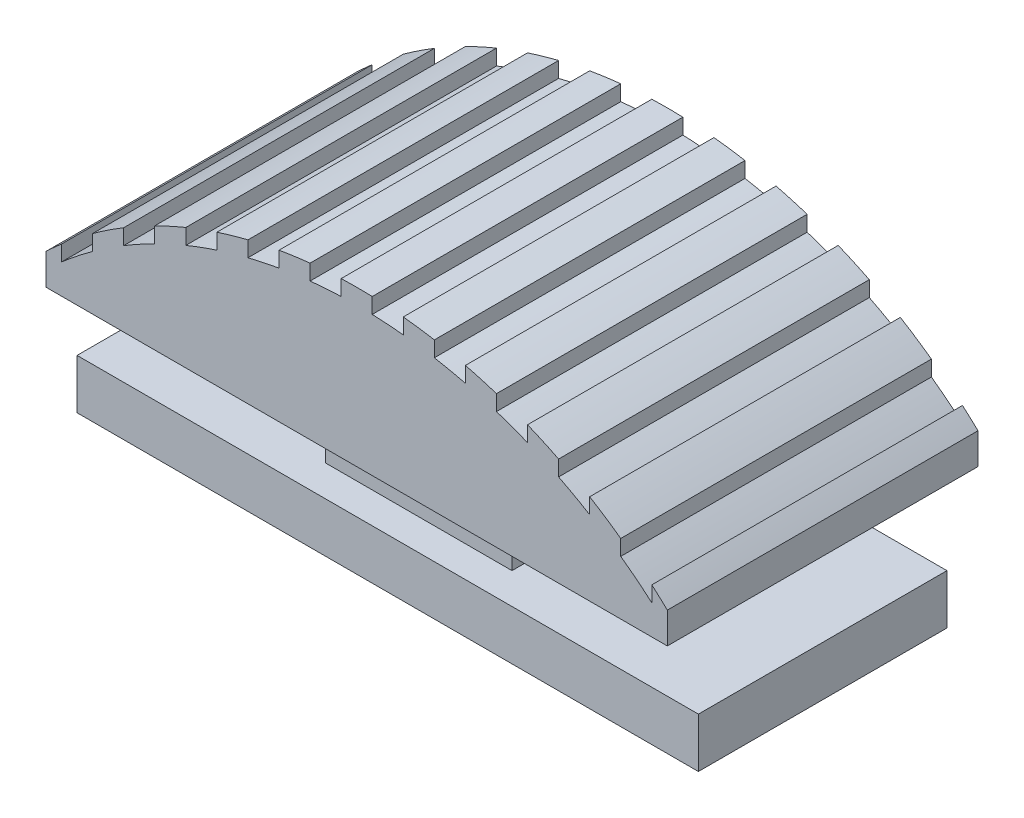
SolidWorks part; units mm, degrees
ref_plane "前视基准面" through (0, 0, 0) normal (0, 0, 1) x (1, 0, 0)
ref_plane "上视基准面" through (0, 0, 0) normal (0, 1, 0) x (1, 0, 0)
ref_plane "右视基准面" through (0, 0, 0) normal (1, 0, 0) x (0, 0, -1)
sketch "草图1" plane through (0, 0, 0) normal (0, 1, 0) x (1, 0, 0)
  line L0 (-4.9469, 0) -> (7.0243, 0) construction
  line L1 (-5, 2.5) -> (5, 2.5)
  line L2 (-5, 2.5) -> (-5, -2.5)
  line L3 (-5, -2.5) -> (5, -2.5)
  line L4 (5, 2.5) -> (5, -2.5)
  line L5 (0, 3.9764) -> (0, -4.0821) construction
  dimension "D1" = 5
  dimension "D2" = 10
extrude "凸台-拉伸1" add sketch "草图1" along normal blind 0.5
sketch "草图2" plane through (0, 0.5, 0) normal (0, 1, 0) x (1, 0, 0)
  line L0 (-5.4747, 0) -> (5.3846, 0) construction
  line L1 (-1.5, 1.5) -> (1.5, 1.5)
  line L2 (-1.5, 1.5) -> (-1.5, -1.5)
  line L3 (-1.5, -1.5) -> (1.5, -1.5)
  line L4 (1.5, 1.5) -> (1.5, -1.5)
  line L5 (0, 3.3379) -> (0, -3.1277) construction
  dimension "D1" = 3
  dimension "D2" = 3
extrude "凸台-拉伸2" add sketch "草图2" along normal blind 0.5
sketch "草图3" plane through (0, 1, 0) normal (0, 1, 0) x (1, 0, 0)
  line L1 (-5, 2.5) -> (5, 2.5)
  line L2 (-5, 2.5) -> (-5, -2.5)
  line L3 (-5, -2.5) -> (5, -2.5)
  line L4 (5, 2.5) -> (5, -2.5)
extrude "凸台-拉伸3" add sketch "草图3" along normal blind 0.5
sketch "草图4" plane through (0, 0, 2.5) normal (0, 0, 1) x (1, 0, 0)
  line L0 (-5, 0) -> (5, 0) construction
  line L1 (-5.959, 3.5) -> (5.2488, 3.5) construction
  line L2 (-5, 1.5) -> (5, 1.5) construction
  line L3 (-5, 1.5) -> (5, 1.5)
  arc A1 (-5, 1.5) -> (5, 1.5) centre (0, -3.75) cw
  dimension "D1" = 2
  dimension "D2" = 3.5
extrude "凸台-拉伸4" add sketch "草图4" against normal up to surface (5 mm away) up to face at (0, 1.25, -2.5)
sketch "草图5" plane through (0, 0, 2.5) normal (0, 0, 1) x (1, 0, 0)
  line L0 (5, 1.5) -> (5, 1) construction
  line L1 (-5, 1.5) -> (-5, 1) construction
  line L2 (-5.4811, 1.25) -> (6.0159, 1.25) construction
  line L3 (-4.75, 3.8262) -> (-4.25, 3.8262)
  line L4 (-4.75, 3.8262) -> (-4.75, 1.4772)
  line L6 (-4.25, 3.8262) -> (-4.25, 1.8737)
  line L7 (-3.75, 3.8262) -> (-3.75, 2.2048)
  line L8 (-3.75, 3.8262) -> (-3.25, 3.8262)
  line L9 (-3.25, 3.8262) -> (-3.25, 2.4807)
  line L11 (-2.75, 3.8262) -> (-2.75, 2.7082)
  line L12 (-2.75, 3.8262) -> (-2.25, 3.8262)
  line L13 (-2.25, 3.8262) -> (-2.25, 2.892)
  line L15 (-1.75, 3.8262) -> (-1.75, 3.0356)
  line L16 (-1.75, 3.8262) -> (-1.25, 3.8262)
  line L17 (-1.25, 3.8262) -> (-1.25, 3.1414)
  line L19 (-0.75, 3.8262) -> (-0.75, 3.2111)
  line L20 (-0.75, 3.8262) -> (-0.25, 3.8262)
  line L21 (-0.25, 3.8262) -> (-0.25, 3.2457)
  line L23 (0.25, 3.8262) -> (0.25, 3.2457)
  line L24 (0.25, 3.8262) -> (0.75, 3.8262)
  line L25 (0.75, 3.8262) -> (0.75, 3.2111)
  line L27 (1.25, 3.8262) -> (1.25, 3.1414)
  line L28 (1.25, 3.8262) -> (1.75, 3.8262)
  line L29 (1.75, 3.8262) -> (1.75, 3.0356)
  line L31 (2.25, 3.8262) -> (2.25, 2.892)
  line L32 (2.25, 3.8262) -> (2.75, 3.8262)
  line L33 (2.75, 3.8262) -> (2.75, 2.7082)
  line L35 (3.25, 3.8262) -> (3.25, 2.4807)
  line L36 (3.25, 3.8262) -> (3.75, 3.8262)
  line L37 (3.75, 3.8262) -> (3.75, 2.2048)
  line L39 (4.25, 3.8262) -> (4.25, 1.8737)
  line L40 (4.25, 3.8262) -> (4.75, 3.8262)
  line L41 (4.75, 3.8262) -> (4.75, 1.4772)
  arc A0 (5, 1.5) -> (-5, 1.5) centre (0, -3.75) ccw construction
  arc A1 (5, 1.5) -> (-5, 1.5) centre (0, -3.75) ccw construction
  arc A2 (5, 1.25) -> (-5, 1.25) centre (0, -4) ccw construction
  arc A3 (-4.75, 1.4772) -> (-4.25, 1.8737) centre (0, -4) cw
  arc A4 (-3.75, 2.2048) -> (-3.25, 2.4807) centre (0, -4) cw
  arc A5 (-2.75, 2.7082) -> (-2.25, 2.892) centre (0, -4) cw
  arc A6 (-1.75, 3.0356) -> (-1.25, 3.1414) centre (0, -4) cw
  arc A7 (-0.75, 3.2111) -> (-0.25, 3.2457) centre (0, -4) cw
  arc A8 (0.25, 3.2457) -> (0.75, 3.2111) centre (0, -4) cw
  arc A9 (1.25, 3.1414) -> (1.75, 3.0356) centre (0, -4) cw
  arc A10 (2.25, 2.892) -> (2.75, 2.7082) centre (0, -4) cw
  arc A11 (3.25, 2.4807) -> (3.75, 2.2048) centre (0, -4) cw
  arc A12 (4.25, 1.8737) -> (4.75, 1.4772) centre (0, -4) cw
  dimension "D1" = 0.5
  dimension "D2" = 0.25
  dimension "D4" = 10
  dimension "D5" = 0.5
extrude "切除-拉伸3" cut sketch "草图5" against normal up to surface (5 mm away) up to face at (0, 1.75, -2.5)
sketch "草图6" plane through (0, 0, 0) normal (0, -1, 0) x (1, 0, 0)
  line L0 (-5.6348, 0) -> (5.5448, 0) construction
  line L1 (0, 3.3379) -> (0, -3.6081) construction
  line L3 (-0.8, 0.8) -> (0.8, 0.8)
  line L4 (-0.8, 0.8) -> (-0.8, -0.8)
  line L5 (-0.8, -0.8) -> (0.8, -0.8)
  line L6 (0.8, 0.8) -> (0.8, -0.8)
  dimension "D1" = 1.6
  dimension "D2" = 1.6
extrude "切除-拉伸4" cut sketch "草图6" against normal blind 2.5
sketch "草图7" plane through (0, 0, 0) normal (0, -1, 0) x (1, 0, 0)
  line L0 (-6.0418, 0) -> (6.0017, 0) construction
  line L1 (-5, 2.5) -> (5, 2.5) construction
  line L2 (5, 2.5) -> (5, -2.5) construction
  line L3 (-5, -2.5) -> (-5, 2.5) construction
  line L5 (0, 3.3716) -> (0, -3.4016) construction
  line L7 (-5, 2.5) -> (5, 2.5)
  line L8 (-5, 2.5) -> (-5, 2)
  line L9 (-5, 2) -> (5, 2)
  line L10 (5, 2.5) -> (5, 2)
  line L11 (-5, -2.5) -> (5, -2.5)
  line L12 (-5, -2.5) -> (-5, -2)
  line L13 (-5, -2) -> (5, -2)
  line L14 (5, -2.5) -> (5, -2)
  dimension "D1" = 4
  dimension "D2" = 10
extrude "切除-拉伸5" cut sketch "草图7" against normal blind 1
sketch "草图8" plane through (0, 0, 0) normal (0, -1, 0) x (1, 0, 0)
  line L1 (-5, 2) -> (5, 2)
  line L2 (-5, 2) -> (-5, -2)
  line L3 (-5, -2) -> (5, -2)
  line L4 (5, 2) -> (5, -2)
extrude "凸台-拉伸5" add sketch "草图8" along normal blind 1
sketch "草图11" plane through (0, 0.5, 0) normal (0, 1, 0) x (1, 0, 0)
  line L0 (-1.5, -1.5) -> (1.5, -1.5) construction
  line L1 (1.5, 1.5) -> (-1.5, 1.5)
  line L2 (1.5, 1.5) -> (1.5, -1.5)
  line L3 (1.5, -1.5) -> (-1.5, -1.5)
  line L4 (-1.5, 1.5) -> (-1.5, -1.5)
  line L5 (-1.5, 1.5) -> (-1.5, -1.5) construction
  line L7 (5, 2) -> (-5, 2)
  line L8 (5, 2) -> (5, -2)
  line L9 (5, -2) -> (-5, -2)
  line L10 (-5, 2) -> (-5, -2)
extrude "切除-拉伸6" cut sketch "草图11" against normal blind 0.7
extrude "切除-拉伸7" cut sketch "草图6<2>" along normal up to next
sketch "草图6<2>" plane through (0, 0, 0) normal (0, -1, 0) x (1, 0, 0) same geometry as "草图6"
